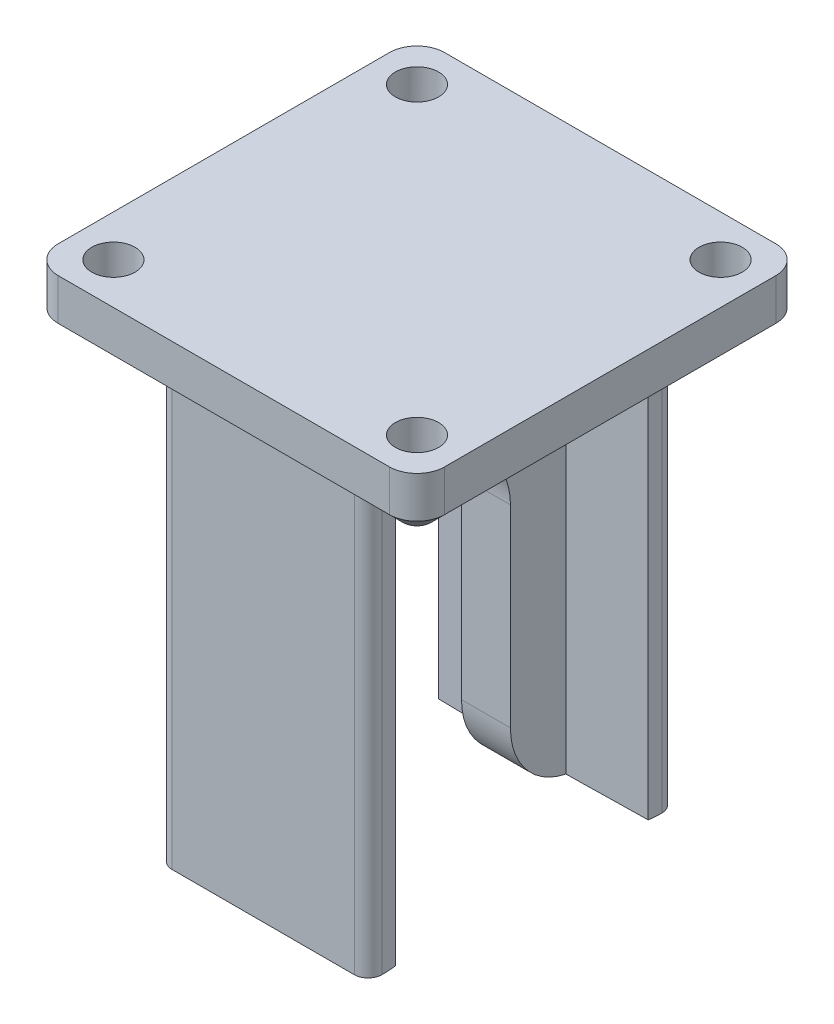
SolidWorks part; units mm, degrees
ref_plane "Front Plane" through (0, 0, 0) normal (0, 0, 1) x (1, 0, 0)
ref_plane "Top Plane" through (0, 0, 0) normal (0, 1, 0) x (1, 0, 0)
ref_plane "Right Plane" through (0, 0, 0) normal (1, 0, 0) x (0, 0, -1)
sketch "Sketch1" plane through (0, 0, 0) normal (0, 1, 0) x (1, 0, 0)
  line L1 (-22.225, -22.225) -> (22.225, -22.225)
  line L2 (-22.225, -22.225) -> (-22.225, 22.225)
  line L3 (-22.225, 22.225) -> (22.225, 22.225)
  line L4 (22.225, -22.225) -> (22.225, 22.225)
  line L5 (-22.225, -22.225) -> (22.225, 22.225) construction
  line L6 (-22.225, 22.225) -> (22.225, -22.225) construction
  point P0 (0, 0)
  dimension "D1" = 44.45
extrude "Boss-Extrude1" add sketch "Sketch1" along normal mid plane 6.35
sketch "Sketch3" plane through (0, -3.175, 0) normal (0, -1, 0) x (1, 0, 0)
  line L0 (2.9404, -4.1) -> (2.9404, -13.6952) construction
  line L1 (2.9404, 13.6952) -> (2.9404, 4.1) construction
  line L2 (9.4404, 14.3) -> (3.4317, 14.1951) construction
  line L3 (11.9404, 14.3873) -> (9.4404, 14.3) construction
  line L4 (11.9404, 2.295) -> (11.9404, 14.3873) construction
  line L5 (11.9404, 2.295) -> (11.9404, -2.295) construction
  line L6 (11.9404, -14.3873) -> (11.9404, -2.295) construction
  line L7 (9.4404, -14.3) -> (11.9404, -14.3873) construction
  line L8 (3.4317, -14.1951) -> (9.4404, -14.3) construction
  line L9 (2.9404, 0) -> (2.9404, -14.1865) construction
  line L10 (2.9404, 14.1865) -> (2.9404, 0) construction
  line L11 (9.4404, 14.3) -> (2.9404, 14.1865) construction
  line L12 (11.9404, 14.3873) -> (9.4404, 14.3) construction
  line L13 (11.9404, 2.295) -> (11.9404, 14.3873) construction
  line L14 (11.9404, 2.295) -> (11.9404, -2.295) construction
  line L15 (11.9404, -14.3873) -> (11.9404, -2.295) construction
  line L16 (9.4404, -14.3) -> (11.9404, -14.3873) construction
  line L17 (2.9404, -14.1865) -> (9.4404, -14.3) construction
  line L18 (0, 0) -> (0, -24.9027) construction
  line L19 (-2.9404, -14.1865) -> (-9.4404, -14.3) construction
  line L20 (-9.4404, -14.3) -> (-11.9404, -14.3873) construction
  line L21 (-11.9404, -14.3873) -> (-11.9404, -2.295) construction
  line L22 (-11.9404, 2.295) -> (-11.9404, -2.295) construction
  line L23 (-11.9404, 2.295) -> (-11.9404, 14.3873) construction
  line L24 (-11.9404, 14.3873) -> (-9.4404, 14.3) construction
  line L25 (-9.4404, 14.3) -> (-2.9404, 14.1865) construction
  line L26 (-2.9404, 14.1865) -> (-2.9404, 0) construction
  line L27 (-2.9404, 0) -> (-2.9404, -14.1865) construction
  line L28 (2.8134, 0) -> (2.8134, -14.3113) construction
  line L29 (2.8134, -14.3113) -> (9.4371, -14.427) construction
  line L30 (9.4371, -14.427) -> (12.0674, -14.5188) construction
  line L31 (12.0674, -14.5188) -> (12.0674, -2.295) construction
  line L32 (12.0674, 2.295) -> (12.0674, -2.295) construction
  line L33 (12.0674, 2.295) -> (12.0674, 14.5188) construction
  line L34 (12.0674, 14.5188) -> (9.4371, 14.427) construction
  line L35 (9.4371, 14.427) -> (2.8134, 14.3113) construction
  line L36 (2.8134, 14.3113) -> (2.8134, 0) construction
  line L37 (-2.8134, -14.3113) -> (-9.4371, -14.427) construction
  line L38 (-9.4371, -14.427) -> (-12.0674, -14.5188) construction
  line L39 (-12.0674, -14.5188) -> (-12.0674, -2.295) construction
  line L40 (-12.0674, 2.295) -> (-12.0674, -2.295) construction
  line L41 (-12.0674, 2.295) -> (-12.0674, 14.5188) construction
  line L42 (-12.0674, 14.5188) -> (-9.4371, 14.427) construction
  line L43 (-9.4371, 14.427) -> (-2.8134, 14.3113) construction
  line L44 (-2.8134, 14.3113) -> (-2.8134, 0) construction
  line L45 (-2.8134, 0) -> (-2.8134, -14.3113) construction
  line L46 (12.0674, 14.5188) -> (2.8134, 14.3113)
  line L47 (-2.8134, 14.3113) -> (-12.0674, 14.5188)
  line L48 (2.8134, 14.3113) -> (2.8134, -14.3113)
  line L49 (2.8134, -14.3113) -> (12.0674, -14.5188)
  line L50 (-2.8134, 14.3113) -> (-2.8134, -14.3113)
  line L51 (-2.8134, -14.3113) -> (-12.0674, -14.5188)
  line L52 (-12.0674, -14.5188) -> (-12.0674, -17.6938)
  line L53 (-12.0674, -17.6938) -> (12.0674, -17.6938)
  line L54 (12.0674, -17.6938) -> (12.0674, -14.5188)
  line L55 (12.0674, 14.5188) -> (12.0674, 17.6938)
  line L56 (12.0674, 17.6938) -> (-12.0674, 17.6938)
  line L57 (-12.0674, 17.6938) -> (-12.0674, 14.5188)
  dimension "D2" = 3.175
  dimension "D1" = 0.127
extrude "Boss-Extrude2" add sketch "Sketch3" along normal blind 50.8
fillet "Fillet1" radius 3.175 4 edges at (22.225, 0, -22.225) (-22.225, 0, -22.225) (-22.225, 0, 22.225) (22.225, 0, 22.225)
fillet "Fillet2" radius 1.5875 4 edges at (-12.0674, -28.575, 17.6938) (12.0674, -28.575, 17.6938) (-12.0674, -28.575, -17.6938) (12.0674, -28.575, -17.6938)
fillet "Fillet3" radius 3.175 6 edges at (-7.4404, -3.175, 14.4151) (-2.8134, -3.175, 0) (-7.4404, -3.175, -14.4151) (7.4404, -3.175, -14.4151) (7.4404, -3.175, 14.4151) (2.8134, -3.175, 0)
sketch "Sketch4" plane through (0, 3.175, 0) normal (0, 1, 0) x (1, 0, 0)
  line L1 (17.4625, -17.4625) -> (-17.4625, -17.4625) construction
  line L2 (17.4625, -17.4625) -> (17.4625, 17.4625) construction
  line L3 (17.4625, 17.4625) -> (-17.4625, 17.4625) construction
  line L4 (-17.4625, -17.4625) -> (-17.4625, 17.4625) construction
  line L5 (17.4625, -17.4625) -> (-17.4625, 17.4625) construction
  line L6 (17.4625, 17.4625) -> (-17.4625, -17.4625) construction
  circle A0 centre (17.4625, 17.4625) radius 2.4892
  circle A1 centre (17.4625, -17.4625) radius 2.4892
  circle A2 centre (-17.4625, -17.4625) radius 2.4892
  circle A3 centre (-17.4625, 17.4625) radius 2.4892
  point P0 (0, 0)
  dimension "D2" = 4.9784
  dimension "D1" = 34.925
extrude "Cut-Extrude1" cut sketch "Sketch4" against normal through all
sketch "Sketch5" plane through (2.8134, 0, 0) normal (1, 0, 0) x (0, 0, -1)
  line L0 (14.3113, -53.975) -> (-14.3113, -53.975) construction
  line L1 (-7.9375, -53.975) -> (7.9375, -53.975)
  line L2 (-7.9375, -53.975) -> (-7.9375, -15.875)
  line L3 (-7.9375, -15.875) -> (7.9375, -15.875)
  line L4 (7.9375, -53.975) -> (7.9375, -15.875)
  point P6 (0, -15.875)
  dimension "D1" = 38.1
  dimension "D2" = 15.875
extrude "Cut-Extrude2" cut sketch "Sketch5" against normal through all
fillet "Fillet4" radius 7.9375 2 edges at (0, -15.875, -7.9375) (0, -15.875, 7.9375)
fillet "Fillet5" radius 7.9375 2 edges at (0, -53.975, -7.9375) (0, -53.975, 7.9375)
chamfer "Chamfer1" distance 1.5875 angle 45 8 edges at (-22.225, -3.175, 0) (-21.2951, -3.175, 21.2951) (-21.2951, -3.175, -21.2951) (0, -3.175, 22.225) (0, -3.175, -22.225) (21.2951, -3.175, 21.2951) (21.2951, -3.175, -21.2951) (22.225, -3.175, 0)
